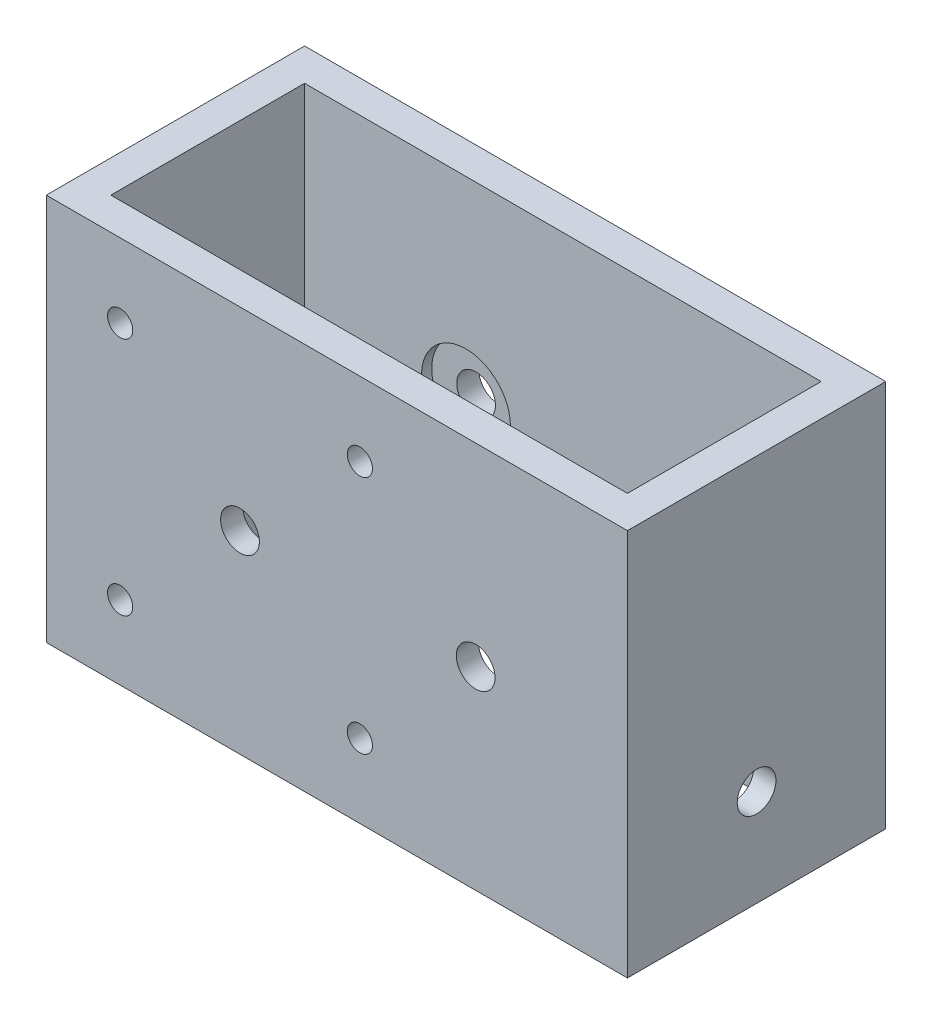
SolidWorks part; units mm, degrees
ref_plane "Front Plane" through (0, 0, 0) normal (0, 0, 1) x (1, 0, 0)
ref_plane "Top Plane" through (0, 0, 0) normal (0, 1, 0) x (1, 0, 0)
ref_plane "Right Plane" through (0, 0, 0) normal (1, 0, 0) x (0, 0, -1)
sketch "Sketch1" plane through (0, 0, 0) normal (0, 1, 0) x (1, 0, 0)
  line L1 (0, 0) -> (114.3, 0)
  line L2 (0, 0) -> (0, -50.8)
  line L3 (0, -50.8) -> (114.3, -50.8)
  line L4 (114.3, 0) -> (114.3, -50.8)
  line L5 (0, 0) -> (114.3, -50.8) construction
  line L6 (0, -50.8) -> (114.3, 0) construction
  line L7 (107.95, -44.45) -> (6.35, -44.45)
  line L8 (107.95, -44.45) -> (107.95, -6.35)
  line L9 (107.95, -6.35) -> (6.35, -6.35)
  line L10 (6.35, -44.45) -> (6.35, -6.35)
  line L11 (107.95, -44.45) -> (6.35, -6.35) construction
  line L12 (107.95, -6.35) -> (6.35, -44.45) construction
  point P4 (57.15, -25.4)
  point P6 (57.15, -25.4)
  dimension "D1" = 114.3
  dimension "D2" = 50.8
  dimension "D3" = 6.35
  dimension "D4" = 6.35
extrude "Boss-Extrude1" add sketch "Sketch1" along normal blind 76.2
sketch "Sketch2" plane through (0, 0, 50.8) normal (0, 0, 1) x (1, 0, 0)
  line L0 (0, 0) -> (114.3, 0) construction
  line L1 (8.89, 67.31) -> (67.31, 67.31) construction
  line L2 (8.89, 67.31) -> (8.89, 8.89) construction
  line L3 (8.89, 8.89) -> (67.31, 8.89) construction
  line L4 (67.31, 67.31) -> (67.31, 8.89) construction
  line L5 (8.89, 67.31) -> (67.31, 8.89) construction
  line L6 (8.89, 8.89) -> (67.31, 67.31) construction
  line L7 (0, 76.2) -> (0, 0) construction
  circle A0 centre (38.1, 38.1) radius 33.3375 construction
  circle A1 centre (14.5268, 61.6732) radius 2.4765
  circle A2 centre (61.6732, 61.6732) radius 2.4765
  circle A3 centre (61.6732, 14.5268) radius 2.4765
  circle A4 centre (14.5268, 14.5268) radius 2.4765
  circle A5 centre (38.1, 38.1) radius 3.81
  point P4 (38.1, 38.1)
  dimension "D3" = 66.675
  dimension "D4" = 4.953
  dimension "D5" = 4.953
  dimension "D6" = 4.953
  dimension "D7" = 4.953
  dimension "D8" = 7.62
  dimension "D1" = 58.42
  dimension "D2" = 58.42
  dimension "D9" = 38.1
  dimension "D10" = 38.1
extrude "Cut-Extrude1" cut sketch "Sketch2" against normal up to next contours A1 | A2 | A3 | A4
extrude "Cut-Extrude2" cut sketch "Sketch2<5>" against normal through all contours A5
sketch "Sketch2<5>" plane through (0, 0, 50.8) normal (0, 0, 1) x (1, 0, 0) same geometry as "Sketch2"
sketch "Sketch5" plane through (0, 0, 50.8) normal (0, 0, 1) x (1, 0, 0)
  line L0 (0, 0) -> (114.3, 0) construction
  line L1 (7.62, 7.62) -> (68.58, 7.62) construction
  line L2 (7.62, 7.62) -> (7.62, 68.58) construction
  line L3 (7.62, 68.58) -> (68.58, 68.58) construction
  line L4 (68.58, 7.62) -> (68.58, 68.58) construction
  line L5 (7.62, 7.62) -> (68.58, 68.58) construction
  line L6 (7.62, 68.58) -> (68.58, 7.62) construction
  circle A0 centre (84.455, 38.1) radius 3.81
  point P0 (38.1, 38.1)
  dimension "D3" = 7.62
  dimension "D1" = 60.96
  dimension "D2" = 60.96
  dimension "D4" = 38.1
  dimension "D5" = 15.875
extrude "Cut-Extrude4" cut sketch "Sketch5" against normal through all
sketch "Sketch6" plane through (0, 0, 0) normal (-1, 0, 0) x (0, 0, 1)
  line L0 (0, 38.1) -> (50.8, 38.1) construction
  line L1 (0, 76.2) -> (0, 0) construction
  line L2 (50.8, 76.2) -> (50.8, 0) construction
  line L3 (25.4, 76.2) -> (25.4, 0) construction
  line L4 (0, 76.2) -> (50.8, 76.2) construction
  line L5 (0, 0) -> (50.8, 0) construction
  circle A0 centre (25.4, 19.05) radius 3.81
  dimension "D2" = 7.62
  dimension "D1" = 19.05
extrude "Cut-Extrude5" cut sketch "Sketch6" against normal through all
sketch "Sketch7" plane through (6.35, 0, 0) normal (1, 0, 0) x (0, 0, -1)
  circle A0 centre (-25.4, 19.05) radius 8.7312
  dimension "D1" = 17.4625
extrude "Cut-Extrude6" cut sketch "Sketch7" against normal blind 1.9844
sketch "Sketch8" plane through (0, 0, 44.45) normal (0, 0, -1) x (-1, 0, 0)
  circle A0 centre (-38.1, 38.1) radius 8.7313
  circle A1 centre (-84.455, 38.1) radius 8.7313
  dimension "D1" = 17.4625
  dimension "D2" = 17.4625
extrude "Cut-Extrude7" cut sketch "Sketch8" against normal blind 1.9844
sketch "Sketch9" plane through (107.95, 0, 0) normal (-1, 0, 0) x (0, 0, 1)
  circle A0 centre (25.4, 19.05) radius 8.7312
  dimension "D1" = 17.4625
extrude "Cut-Extrude8" cut sketch "Sketch9" against normal blind 1.9844
sketch "Sketch10" plane through (0, 0, 6.35) normal (0, 0, 1) x (1, 0, 0)
  circle A0 centre (38.1, 38.1) radius 8.7312
  circle A1 centre (84.455, 38.1) radius 8.7313
  dimension "D1" = 17.4625
  dimension "D2" = 17.4625
extrude "Cut-Extrude9" cut sketch "Sketch10" against normal blind 1.9844
equation "\"wheelPitchD\"= 16mm"
equation "\"wheelClearanceD\"= 18mm"
equation "\"wormPitchD\"= 12mm"
equation "\"wormClearanceD\"= 14mm"
equation "\"ShaftD\"= 0.25in"
equation "\"MountingDistance\" = 14mm"
equation "\"HubDiameter\"= 12mm"
equation "\"HubWidth\"= 8mm"
equation "\"FaceWidth\"= 8mm"
